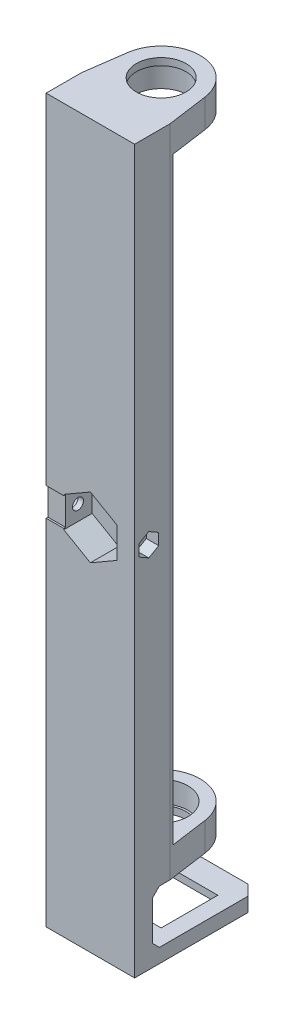
SolidWorks part; units mm, degrees
other "Markup1"
sketch "Sketch20" plane through (12.5, 200, 20) normal (0, 0.0878, 0.9961) x (0.9932, -0.1157, 0.0102)
ref_plane "Front Plane" through (0, 0, 0) normal (0, 0, 1) x (1, 0, 0)
ref_plane "Top Plane" through (0, 0, 0) normal (0, 1, 0) x (1, 0, 0)
ref_plane "Right Plane" through (0, 0, 0) normal (1, 0, 0) x (0, 0, -1)
sketch "Sketch1" plane through (0, 0, 0) normal (0, 1, 0) x (1, 0, 0)
  line L0 (0, 13.844) -> (0, -25.2925) construction
  line L1 (-12.5, -10) -> (-10.8947, 1.5184)
  line L2 (-12.5, -10) -> (-12.5, -20)
  line L3 (-12.5, -20) -> (12.5, -20)
  line L4 (12.5, -10) -> (12.5, -20)
  line L5 (12.5, -10) -> (10.8947, 1.5184)
  arc A0 (10.8947, 1.5184) -> (-10.8947, 1.5184) centre (0, 0) ccw
  point P10 (0, -20)
  dimension "D1" = 22
  dimension "D2" = 25
  dimension "D3" = 10
  dimension "D4" = 10
extrude "Boss-Extrude1" add sketch "Sketch1" along normal blind 200
sketch "Sketch4" plane through (0, 0, 0) normal (0, -1, 0) x (1, 0, 0)
  circle A0 centre (0, 0) radius 7
  dimension "D1" = 14
extrude "Cut-Extrude2" cut sketch "Sketch4" against normal blind 200
sketch "Sketch3" plane through (0, 0, 0) normal (1, 0, 0) x (0, 0, -1)
  line L0 (11, 0) -> (11, 200) construction
  line L1 (11, 192) -> (-9, 192)
  line L2 (11, 192) -> (11, 23)
  line L3 (11, 23) -> (-9, 23)
  line L4 (-9, 192) -> (-9, 23)
  line L5 (11, 200) -> (1.5184, 200) construction
  line L7 (-10, 200) -> (-10, 0) construction
  line L8 (11, 0) -> (-10, 0)
  line L9 (11, 0) -> (11, 15)
  line L10 (11, 15) -> (-10, 15)
  line L11 (-10, 0) -> (-10, 15)
  dimension "D1" = 20
  dimension "D2" = 8
  dimension "D3" = 15
  dimension "D4" = 8
extrude "Cut-Extrude1" cut sketch "Sketch3" against normal mid plane 200
sketch "Sketch5" plane through (0, 192, 0) normal (0, -1, 0) x (1, 0, 0)
  circle A0 centre (0, 0) radius 7.565
  dimension "D1" = 15.13
extrude "Cut-Extrude3" cut sketch "Sketch5" against normal blind 6
sketch "Sketch6" plane through (0, 23, 0) normal (0, 1, 0) x (1, 0, 0)
  circle A0 centre (0, 0) radius 7.565
  dimension "D1" = 15.13
extrude "Cut-Extrude4" cut sketch "Sketch6" against normal blind 6
sketch "Sketch7" plane through (0, 0, 20) normal (0, 0, 1) x (1, 0, 0)
  line L0 (0, 200) -> (0, 0) construction
  line L1 (-12.5, 200) -> (12.5, 200) construction
  line L2 (-12.5, 100) -> (12.5, 100) construction
  line L3 (-12.5, 200) -> (-12.5, 0) construction
  line L4 (12.5, 200) -> (12.5, 0) construction
  circle A0 centre (0, 100) radius 4.85
  dimension "D1" = 9.7
extrude "Boss-Extrude2" [suppressed] add sketch "Sketch7" along normal blind 29 from surface starting at face at (0, 100, 20)
sketch "Sketch9" [suppressed] plane through (0, 0, 49) normal (0, 0, 1) x (1, 0, 0)
  circle A0 centre (0, 100) radius 2.05
  dimension "D1" = 4.1
sketch "Sketch11" plane through (0, 0, 0) normal (0, -1, 0) x (1, 0, 0)
  line L1 (0, -1000) -> (0, 49000) construction
  line L3 (-5.5, 21.5) -> (-5.5, 19.5)
  line L5 (-12.5, 20) -> (12.5, 20) construction
  line L6 (12.5, 21.5) -> (5.5, 21.5) construction
  line L7 (12.5, 21.5) -> (12.5, 19.5) construction
  line L8 (12.5, 19.5) -> (5.5, 19.5) construction
  line L9 (5.5, 21.5) -> (5.5, 19.5) construction
  line L10 (12.5, 20) -> (12.5, 10) construction
  line L11 (-12.5, 19.5) -> (-5.5, 19.5)
  line L12 (-12.5, 21.5) -> (-12.5, 19.5)
  line L13 (-12.5, 21.5) -> (-5.5, 21.5)
  dimension "D1" = 0.5
  dimension "D2" = 2
  dimension "D3" = 7
extrude "Cut-Extrude8" cut sketch "Sketch11" against normal mid plane 8 from offset 100 offset against normal yes
extrude "Cut-Extrude9" [suppressed] cut sketch "Sketch9" against normal blind 4
sketch "Sketch12" plane through (0, 0, 0) normal (0, 0, 1) x (1, 0, 0)
  line L0 (0, 104.75) -> (0, 95.25) construction
  line L1 (-4.75, 100) -> (4.75, 100) construction
  line L2 (1.3973, 101.5) -> (-1.3973, 101.5)
  line L3 (-2.6401, 97.95) -> (3.2254, 97.95) construction
  arc A2 (-1.3973, 101.5) -> (1.3973, 101.5) centre (0, 100) ccw
  dimension "D1" = 4.1
  dimension "D2" = 3.55
extrude "Cut-Extrude10" [suppressed] cut sketch "Sketch12" against normal through all both and the other way through all from surface starting at face at (-4.5, 100, 20)
fillet "Fillet1" [suppressed] radius 2
sketch "Sketch13" plane through (0, 0, 0) normal (0, -1, 0) x (1, 0, 0)
  line L0 (12.5, 20) -> (12.5, 10) construction
  line L1 (-12.5, 20) -> (12.5, 20)
  line L2 (-12.5, 20) -> (-12.5, -12)
  line L3 (-9.5, -15) -> (9.5, -15)
  line L4 (12.5, 20) -> (12.5, -12)
  line L5 (-12.5, -12) -> (-9.5, -15)
  line L6 (-8, 8) -> (8, 8)
  line L7 (-8, 8) -> (-8, -8)
  line L8 (-8, -8) -> (8, -8)
  line L9 (8, 8) -> (8, -8)
  line L10 (9.5, -15) -> (12.5, -12)
  line L12 (-8.5, 8.5) -> (8.5, 8.5) construction
  line L13 (-8.5, 8.5) -> (-8.5, -8.5) construction
  line L14 (-8.5, -8.5) -> (8.5, -8.5) construction
  line L15 (8.5, 8.5) -> (8.5, -8.5) construction
  point P1 (12.5, -15)
  point P2 (-12.5, -15)
  point P11 (0, 8)
  point P13 (8, 0)
  point P22 (0, 8.5)
  point P23 (8.5, 0)
  dimension "D1" = 35
  dimension "D2" = 16
  dimension "D4" = 17
  dimension "D5" = 17
extrude "Boss-Extrude3" add sketch "Sketch13" along normal blind 4
sketch "Sketch14" plane through (-12.5, 0, 0) normal (-1, 0, 0) x (0, 0, 1)
  line L1 (15, 15) -> (10, 15)
  line L2 (15, 15) -> (15, 0)
  line L3 (15, 0) -> (10, 0)
  line L4 (10, 15) -> (10, 0)
  dimension "D1" = 5
extrude "Cut-Extrude11" cut sketch "Sketch14" against normal through all
chamfer "Chamfer1" distance 2 angle 45 2 edges at (0, 15, 15) (0, 0, 15)
sketch "Sketch15" plane through (0, -4, 0) normal (0, -1, 0) x (1, 0, 0)
  line L1 (-11.5, 11.5) -> (11.5, 11.5)
  line L2 (-11.5, 11.5) -> (-11.5, -11.5)
  line L3 (-11.5, -11.5) -> (11.5, -11.5)
  line L4 (11.5, 11.5) -> (11.5, -11.5)
  point P4 (-11.5, 0)
  point P6 (0, -11.5)
  dimension "D1" = 23
  dimension "D2" = 23
extrude "Cut-Extrude12" cut sketch "Sketch15" against normal blind 2
sketch "Sketch16" plane through (0, 0, 20) normal (0, 0, 1) x (1, 0, 0)
  line L0 (12.5, 200) -> (12.5, -4) construction
  line L1 (0, 108.6603) -> (-7.5, 104.3301)
  line L2 (-7.5, 104.3301) -> (-7.5, 95.6699)
  line L3 (-7.5, 95.6699) -> (0, 91.3397)
  line L4 (0, 91.3397) -> (7.5, 95.6699)
  line L5 (7.5, 95.6699) -> (7.5, 104.3301)
  line L6 (7.5, 104.3301) -> (0, 108.6603)
  line L7 (-12.5, 200) -> (-12.5, 104) construction
  line L8 (12.5, -4) -> (-12.5, -4) construction
  circle A0 centre (0, 100) radius 7.5 construction
  dimension "D1" = 15
  dimension "D2" = 12.5
  dimension "D3" = 104
extrude "Cut-Extrude13" cut sketch "Sketch16" against normal blind 8
sketch "Sketch17" plane through (-12.5, 0, 0) normal (-1, 0, 0) x (0, 0, 1)
  line L0 (20, -4) -> (-12, -4) construction
  line L1 (20, 200) -> (20, 104) construction
  circle A0 centre (16, 100) radius 1.55
  dimension "D2" = 3.1
  dimension "D1" = 104
  dimension "D3" = 4
extrude "Cut-Extrude14" cut sketch "Sketch17" against normal through all
sketch "Sketch18" plane through (-12.5, 0, 0) normal (-1, 0, 0) x (0, 0, 1)
  circle A0 centre (16, 100) radius 2.75
  circle A1 centre (16, 100) radius 1.55 construction
  dimension "D1" = 5.5
extrude "Cut-Extrude15" cut sketch "Sketch18" against normal blind 3.5
sketch "Sketch19" plane through (12.5, 0, 0) normal (1, 0, 0) x (0, 0, -1)
  line L0 (-9, 23) -> (-9, 192) construction
  line L1 (-16, 103.2332) -> (-18.8, 101.6166)
  line L2 (-18.8, 101.6166) -> (-18.8, 98.3834)
  line L3 (-18.8, 98.3834) -> (-16, 96.7668)
  line L4 (-16, 96.7668) -> (-13.2, 98.3834)
  line L5 (-13.2, 98.3834) -> (-13.2, 101.6166)
  line L6 (-13.2, 101.6166) -> (-16, 103.2332)
  circle A0 centre (-16, 100) radius 2.8 construction
  dimension "D1" = 5.6
extrude "Cut-Extrude16" cut sketch "Sketch19" against normal blind 3.5
fillet "Fillet2" radius 1 1 edges at (-12.5, 100, 18.75)
